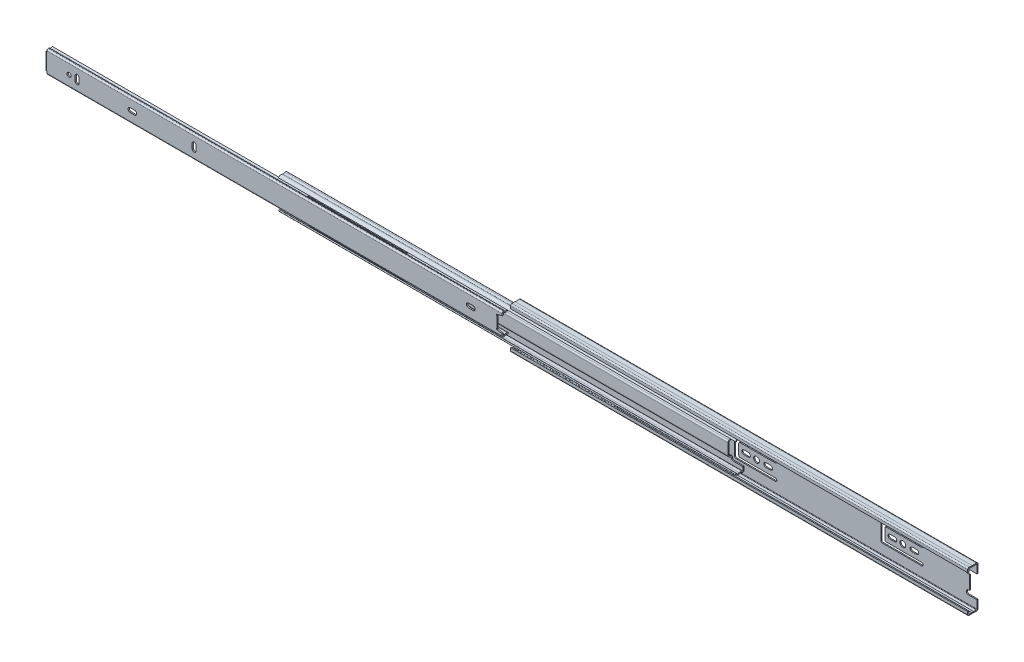
SolidWorks part; units mm, degrees
ref_plane "Front" through (0, 0, 0) normal (0, 0, 1) x (1, 0, 0)
ref_plane "Top" through (0, 0, 0) normal (0, 1, 0) x (1, 0, 0)
ref_plane "Right" through (0, 0, 0) normal (1, 0, 0) x (0, 0, -1)
sketch "Sketch1" plane through (0, 0, 0) normal (1, 0, 0) x (0, 0, -1)
  line L1 (5.6388, 0) -> (-5.6388, 0) construction
  line L4 (-4.1393, 22.8203) -> (-0.7433, 22.6989)
  line L5 (-1.1312, 21.5182) -> (-4.1819, 21.6273)
  line L6 (-4.445, 18.415) -> (-5.6388, 18.415)
  line L7 (-4.445, 21.3734) -> (-4.445, 18.415)
  line L8 (-5.6388, 18.415) -> (-5.6388, 21.3734)
  line L9 (3.9237, 21.6269) -> (0.7619, 21.5441)
  line L10 (5.6388, 0) -> (5.6388, 21.1191)
  line L11 (4.445, 21.1191) -> (4.445, 0)
  line L12 (5.6388, 0) -> (4.445, 0)
  line L13 (-0.7433, 22.6989) -> (3.8925, 22.8203)
  arc A0 (-4.445, 21.3734) -> (-4.1819, 21.6273) centre (-4.191, 21.3734) cw
  arc A1 (-5.6388, 21.3734) -> (-4.1393, 22.8203) centre (-4.191, 21.3734) cw
  arc A3 (3.9237, 21.6269) -> (4.445, 21.1191) centre (3.937, 21.1191) cw
  arc A4 (3.8925, 22.8203) -> (5.6388, 21.1191) centre (3.937, 21.1191) cw
  arc A5 (-1.1312, 21.5182) -> (0.7619, 21.5441) centre (-0.1524, 19.1744) cw
  dimension "D2" = 19.1744
  dimension "D7" = 0.254
  dimension "D8" = 0.508
  dimension "D6" = 2.54
  dimension "D9" = 1.1938
  dimension "D10" = 88.5
  dimension "D1" = 11.2776
  dimension "D3" = 5.7912
  dimension "D4" = 36.83
  dimension "D5" = 1.1938
  dimension "D11" = 87.953
  dimension "D12" = 45.6406
extrude "Extrude1" add sketch "Sketch1" along normal mid plane 500.126
ref_plane "Travel / 2" through (-504.063, 0, 0) normal (-1, 0, 0) x (0, 0, 1)
sketch "Sketch2" plane through (-504.063, 0, 0) normal (-1, 0, 0) x (0, 0, 1)
  line L0 (0.0254, 6.1159) -> (0.0254, 0)
  line L2 (-5.6388, 0) -> (5.6388, 0) construction
  line L3 (5.6388, 21.3734) -> (5.6388, 18.415) construction
  line L7 (-4.445, 21.1191) -> (-4.445, 0) construction
  line L8 (-5.6388, 0) -> (-5.6388, 21.1191) construction
  line L13 (-3.5306, 16.3766) -> (-3.5306, 9.5217)
  line L46 (-2.3867, 7.7262) -> (-0.4146, 6.8065)
  arc A0 (0.0254, 6.1159) -> (-0.4146, 6.8065) centre (-0.7366, 6.1159) ccw
  arc A1 (-1.5056, 17.2916) -> (1.2415, 16.9143) centre (0.1524, 19.1744) ccw
  arc A4 (1.1312, 21.5182) -> (-0.7619, 21.5441) centre (0.1524, 19.1744) ccw construction
  arc A19 (-3.5306, 9.5217) -> (-2.3867, 7.7262) centre (-1.5494, 9.5217) ccw
  arc A25 (-1.5056, 17.2916) -> (-3.5306, 16.3766) centre (-2.3114, 16.3766) ccw
  arc A51 (5.7404, 15.6277) -> (1.2415, 16.9143) centre (2.7686, 13.7451) ccw
  dimension "D2" = 8.4074
  dimension "D3" = 27.4903
  dimension "D6" = 1.9812
  dimension "D8" = 12.2319
  dimension "D10" = 2.5088
  dimension "D11" = 1.2192
  dimension "D4" = 0.762
  dimension "D5" = 4.4704
  dimension "D7" = 115
  dimension "D9" = 19.0435
  dimension "D13" = 11.3792
extrude "Middle Member" add sketch "Sketch2" against normal blind 500.126 separate body thin thin type one direction reverse wall 1.2192
ref_plane "Travel" through (-758.063, 0, 0) normal (-1, 0, 0) x (0, 0, 1)
sketch "Sketch3" plane through (-758.063, 0, 0) normal (-1, 0, 0) x (0, 0, 1)
  line L0 (1.2446, 0) -> (0.0254, 0) construction
  line L1 (-5.6388, 0) -> (-5.6388, 21.1191) construction
  line L56 (7.0612, 0) -> (7.0612, 10.6235)
  line L93 (5.5372, 12.1475) -> (5.1643, 12.1475)
  arc A0 (1.2082, 11.9072) -> (4.2365, 11.8325) centre (2.7686, 13.7451) ccw
  arc A29 (7.0612, 10.6235) -> (5.5372, 12.1475) centre (5.5372, 10.6235) ccw
  arc A53 (5.1643, 12.1475) -> (4.2365, 11.8325) centre (5.1643, 10.6235) ccw
  dimension "D1" = 1.524
  dimension "D4" = 1.524
  dimension "D5" = 2.411
  dimension "D2" = 12.7
  dimension "D3" = 12.1475
  dimension "D6" = 5.853
extrude "Drawer Member" add sketch "Sketch3" against normal blind 500.126 thin thin type one direction wall 1.397
sketch "Sketch6" plane through (0, 0, 7.0612) normal (0, 0, 1) x (1, 0, 0)
  line L1 (-758.063, 0) -> (-756.158, 0)
  line L2 (-758.063, 0) -> (-758.063, 12.1475)
  line L3 (-758.063, 12.1475) -> (-756.158, 12.1475)
  line L4 (-756.158, 0) -> (-756.158, 12.1475)
  line L5 (-257.937, 12.1475) -> (-758.063, 12.1475) construction
  line L7 (-758.063, 10.6235) -> (-758.063, 0) construction
  line L8 (-257.937, 0) -> (-758.063, 0) construction
  dimension "D1" = 1.905
extrude "Cut-Extrude1" cut sketch "Sketch6" against normal through all
sketch "Sketch7" plane through (0, 0, 0) normal (0, -1, 0) x (1, 0, 0)
  line L0 (-756.158, 7.0612) -> (-756.412, 7.0612)
  line L1 (-758.063, 5.4102) -> (-758.063, 0.3041)
  line L2 (-758.063, 0.3041) -> (-756.666, 0.3041)
  line L3 (-756.666, 0.3041) -> (-756.666, 5.4102)
  line L4 (-756.412, 5.6642) -> (-756.158, 5.6642)
  line L5 (-257.937, 5.6642) -> (-756.158, 5.6642) construction
  line L6 (-756.158, 7.0612) -> (-756.158, 5.6642)
  line L7 (-257.937, 0.3041) -> (-756.158, 0.3041) construction
  line L9 (-756.158, 5.087) -> (-756.158, 0.3041) construction
  arc A0 (-756.412, 5.6642) -> (-756.666, 5.4102) centre (-756.412, 5.4102) ccw
  arc A1 (-756.412, 7.0612) -> (-758.063, 5.4102) centre (-756.412, 5.4102) ccw
  dimension "D1" = 0.254
  dimension "D2" = 1.905
extrude "Extrude4" add sketch "Sketch7" against normal blind 8.89
sketch "Sketch8" plane through (0, 0, -4.445) normal (0, 0, 1) x (1, 0, 0)
  line L0 (240.4245, 7.6456) -> (241.8588, 7.493)
  line L1 (250.063, 12.2048) -> (240.6664, 12.2048)
  line L2 (241.8588, 7.493) -> (241.8588, 0)
  line L3 (250.063, 0) -> (-250.063, 0) construction
  line L4 (250.063, 21.1191) -> (250.063, 0) construction
  line L5 (250.063, 12.2048) -> (250.063, 0)
  line L6 (250.063, 0) -> (241.8588, 0)
  arc A0 (240.6664, 12.2048) -> (240.4245, 7.6456) centre (240.6664, 9.9188) ccw
  dimension "D3" = 9.9188
  dimension "D1" = 12.2048
  dimension "D2" = 8.2042
  dimension "D4" = 9.3966
  dimension "D5" = 7.493
extrude "Cut-Extrude2" cut sketch "Sketch8" against normal up to next (1.1938 mm away)
sketch "Sketch11" plane through (0, 0, 7.0612) normal (0, 0, 1) x (1, 0, 0)
  line L0 (-263.652, 5.9678) -> (-263.652, 0)
  line L8 (-257.937, 8.5893) -> (-263.7963, 7.2212)
  line L11 (-263.652, 0) -> (-257.937, 0)
  line L12 (-257.937, 0) -> (-257.937, 8.5893)
  arc A1 (-263.7963, 7.2212) -> (-263.652, 5.9678) centre (-263.6519, 6.6028) ccw
  dimension "D3" = 0.635
  dimension "D1" = 5.715
  dimension "D2" = 8.5893
  dimension "D4" = 5.9678
  dimension "D5" = 103.143
extrude "Cut-Extrude3" cut sketch "Sketch11" against normal up to next (1.397 mm away)
sketch "Sketch12" plane through (0, 0, 1.2446) normal (0, 0, 1) x (1, 0, 0)
  line L0 (-3.937, 12.065) -> (-14.097, 12.065)
  line L1 (-3.937, 16.3766) -> (-3.937, 9.5217) construction
  line L2 (-16.637, 9.525) -> (-16.637, 0)
  line L3 (-3.937, 0) -> (-504.063, 0) construction
  line L4 (-16.637, 0) -> (-3.937, 0)
  line L5 (-3.937, 0) -> (-3.937, 12.065)
  arc A0 (-14.097, 12.065) -> (-16.637, 9.525) centre (-14.097, 9.525) ccw
  point P11 (-16.637, 12.065)
  dimension "D3" = 2.54
  dimension "D1" = 12.7
  dimension "D2" = 12.065
extrude "Cut-Extrude4" cut sketch "Sketch12" against normal through all
sketch "Sketch13" plane through (0, 0, -4.445) normal (0, 0, 1) x (1, 0, 0)
  line L0 (-181.6747, 7.112) -> (-206.5032, 7.112)
  line L1 (241.8588, 0) -> (-250.063, 0) construction
  line L2 (-189.7646, 0) -> (-189.7646, 4.2392) construction
  line L3 (-232.6017, 10.287) -> (-181.6747, 10.287)
  line L4 (-250.063, 21.1191) -> (-250.063, 0) construction
  line L5 (-210.3132, 7.112) -> (-232.6017, 7.112)
  line L6 (-209.5512, 0) -> (-209.5512, 6.35)
  line L7 (-207.2652, 6.35) -> (-207.2652, 0)
  line L8 (-187.2881, 2.286) -> (-192.2411, 2.286)
  line L13 (-226.3406, 0) -> (-221.7686, 0)
  line L14 (-218.238, 0) -> (-211.888, 0)
  line L15 (-209.5512, 0) -> (-207.2652, 0)
  line L16 (-204.7506, 0) -> (-200.1786, 0)
  line L17 (-194.5271, 0) -> (-185.0021, 0)
  arc A1 (-232.6017, 10.287) -> (-232.6017, 7.112) centre (-232.6017, 8.6995) ccw
  arc A2 (-209.5512, 6.35) -> (-210.3132, 7.112) centre (-210.3132, 6.35) ccw
  arc A4 (-206.5032, 7.112) -> (-207.2652, 6.35) centre (-206.5032, 6.35) ccw
  arc A7 (-181.6747, 7.112) -> (-181.6747, 10.287) centre (-181.6747, 8.6995) ccw
  arc A8 (-211.888, 0) -> (-218.238, 0) centre (-215.063, 0) ccw
  arc A9 (-221.7686, 0) -> (-226.3406, 0) centre (-224.0546, 0) ccw
  arc A10 (-200.1786, 0) -> (-204.7506, 0) centre (-202.4646, 0) ccw
  arc A11 (-185.0021, 0) -> (-187.2881, 2.286) centre (-187.2881, 0) ccw
  arc A12 (-192.2411, 2.286) -> (-194.5271, 0) centre (-192.2411, 0) ccw
  dimension "D3" = 2.286
  dimension "D4" = 3.175
  dimension "D7" = 8.9916
  dimension "D8" = 21.59
  dimension "D9" = 34.29
  dimension "D10" = 0.762
  dimension "D11" = 17.5387
  dimension "D12" = 9.525
  dimension "D13" = 5.5118
  dimension "D14" = 35
  dimension "D1" = 3.175
  dimension "D2" = 50.927
  dimension "D5" = 2.286
  dimension "D6" = 10.287
extrude "Cut-Extrude5" cut sketch "Sketch13" against normal up to next (1.1938 mm away)
sketch "Sketch32" plane through (0, 0, -5.6388) normal (0, 0, -1) x (-1, 0, 0)
  line L0 (69.6005, 0) -> (79.1255, 0)
  line L1 (83.888, 0) -> (90.238, 0)
  line L2 (93.7305, 0) -> (103.2555, 0)
  line L3 (106.621, 0) -> (111.193, 0)
  line L4 (-241.8588, 0) -> (185.0021, 0) construction
  line L5 (232.6017, 10.287) -> (181.6747, 10.287) construction
  line L6 (181.6747, 7.112) -> (206.5032, 7.112) construction
  line L7 (98.493, 2.286) -> (98.493, -3.4269) construction
  line L8 (74.363, 2.286) -> (74.363, -3.4269) construction
  line L14 (66.4255, 10.287) -> (109.669, 10.287)
  line L15 (105.097, 7.112) -> (66.4255, 7.112)
  line L17 (111.193, 8.763) -> (111.193, 0)
  line L18 (106.621, 0) -> (106.621, 5.588)
  line L23 (71.8865, 2.286) -> (76.8395, 2.286)
  line L25 (96.0165, 2.286) -> (100.9695, 2.286)
  arc A0 (218.238, 0) -> (211.888, 0) centre (215.063, 0) ccw construction
  arc A13 (111.193, 8.763) -> (109.669, 10.287) centre (109.669, 8.763) ccw
  arc A14 (106.621, 5.588) -> (105.097, 7.112) centre (105.097, 5.588) ccw
  arc A17 (66.4255, 10.287) -> (66.4255, 7.112) centre (66.4255, 8.6995) ccw
  arc A20 (79.1255, 0) -> (76.8395, 2.286) centre (76.8395, 0) ccw
  arc A21 (71.8865, 2.286) -> (69.6005, 0) centre (71.8865, 0) ccw
  arc A22 (90.238, 0) -> (83.888, 0) centre (87.063, 0) ccw
  arc A24 (103.2555, 0) -> (100.9695, 2.286) centre (100.9695, 0) ccw
  arc A25 (96.0165, 2.286) -> (93.7305, 0) centre (96.0165, 0) ccw
  dimension "D2" = 1.524
  dimension "D3" = 3.175
  dimension "D4" = 9.525
  dimension "D5" = 2.286
  dimension "D6" = 11.43
  dimension "D7" = 12.7
  dimension "D8" = 24.13
  dimension "D9" = 20.6375
  dimension "D10" = 128
  dimension "D1" = 4.572
extrude "Cut-Extrude14" cut sketch "Sketch32" against normal up to next (1.1938 mm away)
sketch "Sketch33" plane through (83.6094, 0.8125, -5.6388) normal (0, 0, -1) x (-1, 0, 0)
  line L0 (57.2099, -0.8125) -> (66.7349, -0.8125)
  line L1 (71.4974, -0.8125) -> (77.8474, -0.8125)
  line L2 (81.3399, -0.8125) -> (90.8649, -0.8125)
  line L3 (94.2304, -0.8125) -> (98.8024, -0.8125)
  line L7 (86.1024, 1.4735) -> (86.1024, -4.2394) construction
  line L8 (61.9724, 1.4735) -> (61.9724, -3.4269) construction
  line L9 (-158.2494, -0.8125) -> (153.2099, -0.8125) construction
  line L10 (193.2784, 9.4745) -> (150.0349, 9.4745) construction
  line L11 (150.0349, 6.2995) -> (188.7064, 6.2995) construction
  line L14 (54.0349, 9.4745) -> (97.2784, 9.4745)
  line L15 (92.7064, 6.2995) -> (54.0349, 6.2995)
  line L17 (98.8024, 7.9505) -> (98.8024, -0.8125)
  line L18 (94.2304, -0.8125) -> (94.2304, 4.7755)
  line L23 (59.4959, 1.4735) -> (64.4489, 1.4735)
  line L25 (83.6259, 1.4735) -> (88.5789, 1.4735)
  arc A1 (301.8474, -0.8125) -> (295.4974, -0.8125) centre (298.6724, -0.8125) ccw construction
  arc A13 (98.8024, 7.9505) -> (97.2784, 9.4745) centre (97.2784, 7.9505) ccw
  arc A14 (94.2304, 4.7755) -> (92.7064, 6.2995) centre (92.7064, 4.7755) ccw
  arc A17 (54.0349, 9.4745) -> (54.0349, 6.2995) centre (54.0349, 7.887) ccw
  arc A20 (66.7349, -0.8125) -> (64.4489, 1.4735) centre (64.4489, -0.8125) ccw
  arc A21 (59.4959, 1.4735) -> (57.2099, -0.8125) centre (59.4959, -0.8125) ccw
  arc A22 (77.8474, -0.8125) -> (71.4974, -0.8125) centre (74.6724, -0.8125) ccw
  arc A24 (90.8649, -0.8125) -> (88.5789, 1.4735) centre (88.5789, -0.8125) ccw
  arc A25 (83.6259, 1.4735) -> (81.3399, -0.8125) centre (83.6259, -0.8125) ccw
  dimension "D2" = 1.524
  dimension "D3" = 3.175
  dimension "D4" = 9.525
  dimension "D5" = 2.286
  dimension "D6" = 11.43
  dimension "D7" = 12.7
  dimension "D8" = 24.13
  dimension "D9" = 20.6375
  dimension "D10" = 224
  dimension "D1" = 4.572
extrude "Cut-Extrude6" cut sketch "Sketch33" against normal up to next (1.1938 mm away)
sketch "Sketch34" plane through (169.8236, 1.4527, -5.6388) normal (0, 0, -1) x (-1, 0, 0)
  line L0 (-16.6239, -1.4527) -> (-7.0989, -1.4527)
  line L1 (-2.3364, -1.4527) -> (4.0136, -1.4527)
  line L2 (7.5061, -1.4527) -> (17.0311, -1.4527)
  line L3 (20.3966, -1.4527) -> (24.9686, -1.4527)
  line L4 (-72.0352, -1.4527) -> (143.4241, -1.4527) construction
  line L7 (12.2686, 0.8333) -> (12.2686, -4.8796) construction
  line L8 (-11.8614, 0.8333) -> (-11.8614, -4.0671) construction
  line L9 (279.4926, 8.8343) -> (236.2491, 8.8343) construction
  line L10 (236.2491, 5.6593) -> (274.9206, 5.6593) construction
  line L14 (-19.7989, 8.8343) -> (23.4446, 8.8343)
  line L15 (18.8726, 5.6593) -> (-19.7989, 5.6593)
  line L17 (24.9686, 7.3103) -> (24.9686, -1.4527)
  line L18 (20.3966, -1.4527) -> (20.3966, 4.1353)
  line L23 (-14.3379, 0.8333) -> (-9.3849, 0.8333)
  line L25 (9.7921, 0.8333) -> (14.7451, 0.8333)
  arc A0 (388.0616, -1.4527) -> (381.7116, -1.4527) centre (384.8866, -1.4527) ccw construction
  arc A13 (24.9686, 7.3103) -> (23.4446, 8.8343) centre (23.4446, 7.3103) ccw
  arc A14 (20.3966, 4.1353) -> (18.8726, 5.6593) centre (18.8726, 4.1353) ccw
  arc A17 (-19.7989, 8.8343) -> (-19.7989, 5.6593) centre (-19.7989, 7.2468) ccw
  arc A20 (-7.0989, -1.4527) -> (-9.3849, 0.8333) centre (-9.3849, -1.4527) ccw
  arc A21 (-14.3379, 0.8333) -> (-16.6239, -1.4527) centre (-14.3379, -1.4527) ccw
  arc A22 (4.0136, -1.4527) -> (-2.3364, -1.4527) centre (0.8386, -1.4527) ccw
  arc A24 (17.0311, -1.4527) -> (14.7451, 0.8333) centre (14.7451, -1.4527) ccw
  arc A25 (9.7921, 0.8333) -> (7.5061, -1.4527) centre (9.7921, -1.4527) ccw
  dimension "D2" = 1.524
  dimension "D3" = 3.175
  dimension "D4" = 9.525
  dimension "D5" = 2.286
  dimension "D6" = 11.43
  dimension "D7" = 12.7
  dimension "D8" = 24.13
  dimension "D9" = 20.6375
  dimension "D10" = 384.048
  dimension "D1" = 4.572
extrude "Cut E" cut sketch "Sketch34" against normal up to next (1.1938 mm away)
sketch "Sketch24" plane through (0, 0, 7.0612) normal (0, 0, 1) x (1, 0, 0)
  line L0 (-263.652, 0) -> (-756.412, 0) construction
  line L1 (-723.011, 4.826) -> (-723.011, 0) construction
  line L2 (-725.1954, 2.6416) -> (-725.1954, 0)
  line L3 (-725.1954, 0) -> (-720.8266, 0)
  line L4 (-720.8266, 0) -> (-720.8266, 2.6416)
  line L5 (-667.3215, 0) -> (-657.7965, 0)
  line L6 (-665.0355, 2.286) -> (-660.0825, 2.286)
  line L8 (-597.1954, 2.6416) -> (-597.1954, 0)
  line L9 (-597.1954, 0) -> (-592.8266, 0)
  line L10 (-592.8266, 0) -> (-592.8266, 2.6416)
  line L11 (-758.063, 8.89) -> (-758.063, 0) construction
  line L12 (-662.559, 2.286) -> (-662.559, 0) construction
  circle A0 centre (-731.901, 0) radius 2.1844
  arc A1 (-725.1954, 2.6416) -> (-720.8266, 2.6416) centre (-723.011, 2.6416) cw
  arc A2 (-667.3215, 0) -> (-665.0355, 2.286) centre (-665.0355, 0) cw
  arc A3 (-660.0825, 2.286) -> (-657.7965, 0) centre (-660.0825, 0) cw
  arc A4 (-597.1954, 2.6416) -> (-592.8266, 2.6416) centre (-595.011, 2.6416) cw
  dimension "D1" = 4.3688
  dimension "D4" = 8.89
  dimension "D5" = 2.286
  dimension "D7" = 60.452
  dimension "D8" = 128
  dimension "D2" = 35.052
  dimension "D3" = 4.826
  dimension "D6" = 9.525
extrude "Cut-Extrude13" cut sketch "Sketch24" against normal up to next (1.397 mm away)
sketch "Sketch25" plane through (0, 0, 7.0612) normal (0, 0, 1) x (1, 0, 0)
  line L1 (-263.652, 0) -> (-592.8266, 0) construction
  line L5 (-287.4645, 0) -> (-296.9895, 0)
  line L6 (-660.0825, 2.286) -> (-665.0355, 2.286) construction
  line L7 (-294.7035, 2.286) -> (-289.7505, 2.286)
  line L8 (-292.227, 0) -> (-292.227, 2.286) construction
  arc A1 (-720.8266, 2.6416) -> (-725.1954, 2.6416) centre (-723.011, 2.6416) ccw construction
  arc A3 (-294.7035, 2.286) -> (-296.9895, 0) centre (-294.7035, 0) ccw
  arc A4 (-289.7505, 2.286) -> (-287.4645, 0) centre (-289.7505, 0) cw
  arc A5 (-657.7965, 0) -> (-660.0825, 2.286) centre (-660.0825, 0) ccw construction
  dimension "D1" = 430.784
extrude "Cut D" cut sketch "Sketch25" against normal up to next (1.397 mm away)
sketch "Sketch36" plane through (0, 0, 7.0612) normal (0, 0, 1) x (1, 0, 0)
  line L0 (-309.1954, 0) -> (-304.8266, 0)
  line L1 (-304.8266, 0) -> (-304.8266, 2.6416)
  line L2 (-309.1954, 2.6416) -> (-309.1954, 0)
  line L4 (-296.9895, 0) -> (-592.8266, 0) construction
  line L5 (-720.8266, 0) -> (-720.8266, 2.6416) construction
  arc A0 (-304.8266, 2.6416) -> (-309.1954, 2.6416) centre (-307.011, 2.6416) ccw
  circle A1 centre (-319.711, 0) radius 2.1844
  arc A5 (-720.8266, 2.6416) -> (-725.1954, 2.6416) centre (-723.011, 2.6416) ccw construction
  dimension "D1" = 4.3688
  dimension "D2" = 416
  dimension "D3" = 12.7
extrude "Cut B" [suppressed] cut sketch "Sketch36" against normal up to next
sketch "Sketch38" plane through (0, 0, 7.0612) normal (0, 0, 1) x (1, 0, 0)
  line L0 (-501.1954, 0) -> (-501.1954, 2.6416)
  line L1 (-296.9895, 0) -> (-592.8266, 0) construction
  line L2 (-496.8266, 2.6416) -> (-496.8266, 0)
  line L3 (-496.8266, 0) -> (-501.1954, 0)
  line L4 (-720.8266, 0) -> (-720.8266, 2.6416) construction
  line L5 (-492.28, 0) -> (-484.406, 0)
  line L6 (-492.28, 0) -> (-492.28, 2.3749)
  line L7 (-492.28, 2.3749) -> (-484.406, 2.3749)
  line L8 (-484.406, 0) -> (-484.406, 2.3749)
  line L9 (-499.011, 7.182) -> (-499.011, -4.0911) construction
  line L10 (-505.742, 0) -> (-513.616, 0)
  line L11 (-505.742, 0) -> (-505.742, 2.3749)
  line L12 (-505.742, 2.3749) -> (-513.616, 2.3749)
  line L13 (-513.616, 0) -> (-513.616, 2.3749)
  line L14 (-488.343, 2.3749) -> (-488.343, -3.2385) construction
  arc A0 (-501.1954, 2.6416) -> (-496.8266, 2.6416) centre (-499.011, 2.6416) cw
  arc A1 (-720.8266, 2.6416) -> (-725.1954, 2.6416) centre (-723.011, 2.6416) ccw construction
  dimension "D4" = 224
  dimension "D1" = 7.874
  dimension "D2" = 2.3749
  dimension "D3" = 10.668
extrude "Cut A" [suppressed] cut sketch "Sketch38" against normal up to next
ref_plane "Plane3" through (-237.363, 0, 0) normal (-1, 0, 0) x (0, 0, 1)
sketch "Sketch27" plane through (-237.363, 0, 0) normal (-1, 0, 0) x (0, 0, 1)
  line L0 (0.1524, 21.6832) -> (0.1524, 16.6656)
  line L1 (0.1524, 23.635) -> (0.1524, 15.2838) construction
  arc A0 (0.1524, 16.6656) -> (0.1524, 21.6832) centre (0.1524, 19.1744) ccw
  arc A1 (-1.5056, 17.2916) -> (1.2415, 16.9143) centre (0.1524, 19.1744) ccw construction
revolve "Revolve1" add sketch "Sketch27" angle 360 about L1
pattern_linear "LPattern1" count 6 spacing 19.05 along (1, 0, 0) of bodies 128
sketch "Sketch28" plane through (-237.363, 0, 0) normal (-1, 0, 0) x (0, 0, 1)
  line L0 (2.6612, 19.1744) -> (-2.3564, 19.1744) construction
  line L1 (3.9624, 18.7934) -> (-3.6576, 18.7934)
  line L2 (3.9624, 18.7934) -> (3.9624, 19.5554)
  line L3 (3.9624, 19.5554) -> (-3.6576, 19.5554)
  line L4 (-3.6576, 18.7934) -> (-3.6576, 19.5554)
  line L5 (0.1524, 20.5465) -> (0.1524, 17.804) construction
  circle A1 centre (0.1524, 19.1744) radius 2.5088 construction
  point P8 (0.1524, 19.1744)
  dimension "D1" = 7.62
  dimension "D2" = 0.762
extrude "Extrude7" add sketch "Sketch28" along normal blind 6.35 and the other way blind 101.6
ref_plane "Plane4" through (-465.963, 0, 0) normal (-1, 0, 0) x (0, 0, 1)
sketch "Sketch29" plane through (-465.963, 0, 0) normal (-1, 0, 0) x (0, 0, 1)
  line L0 (2.7686, 16.0438) -> (2.7686, 11.4464)
  line L1 (2.7686, 16.6801) -> (2.7686, 10.2973) construction
  arc A0 (2.7686, 11.4464) -> (2.7686, 16.0438) centre (2.7686, 13.7451) ccw
  arc A1 (4.7105, 14.9753) -> (1.7707, 15.816) centre (2.7686, 13.7451) ccw construction
revolve "Revolve2" add sketch "Sketch29" angle 360 about L1
pattern_linear "LPattern2" count 6 spacing 19.05 along (1, 0, 0) of bodies 135
sketch "Sketch30" plane through (-465.963, 0, 0) normal (-1, 0, 0) x (0, 0, 1)
  line L0 (0.4699, 13.7451) -> (5.0673, 13.7451) construction
  line L1 (3.9624, 18.7934) -> (3.9624, 19.5554) construction
  line L2 (0.2286, 14.1261) -> (5.3086, 14.1261)
  line L3 (0.2286, 14.1261) -> (0.2286, 13.3641)
  line L4 (0.2286, 13.3641) -> (5.3086, 13.3641)
  line L5 (5.3086, 14.1261) -> (5.3086, 13.3641)
  line L7 (2.7686, 14.2437) -> (2.7686, 12.7853) construction
  circle A0 centre (2.7686, 13.7451) radius 2.2987 construction
  point P4 (2.7686, 13.7451)
  dimension "D1" = 5.08
extrude "Extrude8" add sketch "Sketch30" along normal blind 6.35 and the other way blind 101.6
mirror "Mirror3" about plane through (0, 0, 0) normal (0, 1, 0) of bodies 126 119 164 117 124 127 159
mirror "Mirror5" about plane through (0, 0, 0) normal (0, 1, 0) of bodies 141 134
sketch "Sketch39" plane through (0, 0, -5.6388) normal (0, 0, -1) x (-1, 0, 0)
  line L0 (-250.063, 12.2048) -> (-250.063, -12.2048)
  line L1 (-250.063, 0) -> (-241.8588, 0)
  line L2 (-241.8588, -7.493) -> (-241.8588, 7.493) construction
  point P2 (-250.063, 0)
